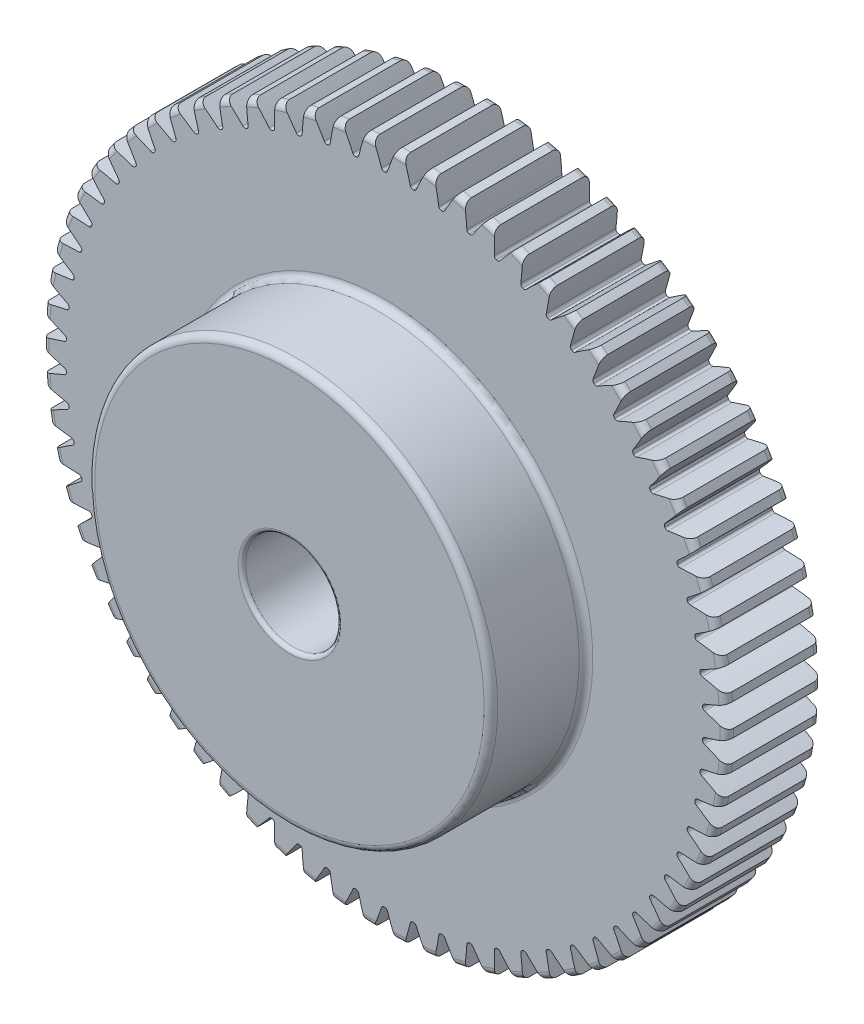
SolidWorks part; units mm, degrees
material "AISI 1020"
ref_plane "Front Plane" through (0, 0, 0) normal (0, 0, 1) x (1, 0, 0)
ref_plane "Top Plane" through (0, 0, 0) normal (0, 1, 0) x (1, 0, 0)
ref_plane "Right Plane" through (0, 0, 0) normal (1, 0, 0) x (0, 0, -1)
sketch "Sketch1" plane through (0, 0, 0) normal (0, 0, 1) x (1, 0, 0)
  line L0 (-889, 0) -> (889, 0) construction
  circle A0 centre (0, 0) radius 45.72 construction
  circle A1 centre (0, 0) radius 44.45 construction
  circle A2 centre (0, 0) radius 42.545 construction
  circle A3 centre (0, 0) radius 26.924 construction
  circle A4 centre (0, 0) radius 6.35 construction
  dimension "D2" = 1.27
  dimension "D3" = 3.175
  dimension "D1" = 3.175
sketch "Sketch2" plane through (0, 0, 0) normal (1, 0, 0) x (0, 0, -1)
  line L0 (0, 0) -> (-12.7, 0) construction
  line L1 (-12.7, 0) -> (-25.4, 0) construction
  dimension "Overall Width" = 25.4
  dimension "Face Width" = 12.7
sketch "Sketch4" plane through (0, 0, 0) normal (1, 0, 0) x (0, 0, -1)
  line L0 (-25.4, 6.35) -> (-25.4, 26.924)
  line L1 (-25.4, 26.924) -> (-12.7, 26.924)
  line L2 (-12.7, 26.924) -> (-12.7, 45.72)
  line L3 (-12.7, 45.72) -> (0, 45.72)
  line L4 (0, 45.72) -> (0, 6.35)
  line L5 (-12.7, 26.924) -> (-12.7, 0) construction
  line L6 (0, 45.72) -> (0, -45.72) construction
  line L7 (-12.7, 26.924) -> (0, 26.924) construction
  line L12 (-25.4, 6.35) -> (0, 6.35)
revolve "Revolve1" add sketch "Sketch4" angle 360 about L1
fillet "Fillet2" radius 0.9144 4 edges at (0, 26.924, 25.4) (0, 26.924, 12.7) (0, 45.72, 12.7) (0, 45.72, 0)
sketch "Sketch7" plane through (0, 0, 12.7) normal (0, 0, 1) x (1, 0, 0)
  line L0 (0, 0) -> (0, 45.72) construction
  line L1 (0.9974, 44.4388) -> (1.4871, 45.6958) construction
  line L3 (2.0512, 45.674) -> (1.9942, 44.4052) construction
  line L4 (1.9942, 44.4052) -> (1.9088, 42.5022) construction
  line L5 (0, 0) -> (1.9088, 42.5022) construction
  line L6 (0.9974, 44.4388) -> (0, 0) construction
  line L7 (0.9974, 44.4388) -> (1.0259, 45.7085) construction
  line L8 (0.9974, 44.4388) -> (0, 0) construction
  circle A0 centre (0, 0) radius 45.72 construction
  arc A1 (-0.0358, 42.545) -> (0.0358, 42.545) centre (0, 0) cw
  circle A2 centre (0, 0) radius 42.545 construction
  arc A3 (-0.9974, 44.4388) -> (0.9974, 44.4388) centre (0, 0) cw construction
  circle A4 centre (0, 0) radius 44.45 construction
  arc A5 (2.5931, 45.6464) -> (1.509, 45.6951) centre (0, 0) ccw construction
  arc A6 (0.9974, 44.4388) -> (2.9901, 44.3493) centre (0, 0) cw construction
  arc A7 (-1.509, 45.6951) -> (1.509, 45.6951) centre (0, 0) cw
  arc A8 (0.3963, 42.8017) -> (1.509, 45.6951) centre (42.4151, 28.3026) cw
  arc A9 (-0.3963, 42.8017) -> (-1.509, 45.6951) centre (-42.4151, 28.3026) ccw
  arc A10 (-0.0358, 42.545) -> (-0.3963, 42.8017) centre (-0.0361, 42.926) cw
  arc A11 (0.0358, 42.545) -> (0.3963, 42.8017) centre (0.0361, 42.926) ccw
  point P26 (-0.3082, 42.5439)
  point P29 (0.3082, 42.5439)
  dimension "D4" = 0.381
  dimension "D5" = 44.45
  dimension "D3" = 20
  dimension "D1" = 3.9898
  dimension "D2" = 1.9949
extrude "Cut-Extrude2" cut sketch "Sketch7" against normal through all
pattern_circular "CirPattern1" count 70 over 360 about axis through (0, 0, 25.4) along (0, 0, -1) of "Cut-Extrude2"
fillet "Fillet3" radius 0.508 2 edges at (0, 6.35, 0) (0, 6.35, 25.4)
sketch "Sketch8" plane through (0, 0, 0) normal (0, 0, -1) x (-1, 0, 0)
  line L1 (-1.651, 7.7826) -> (1.651, 7.7826)
  line L2 (-1.651, 7.7826) -> (-1.651, 4.4806)
  line L3 (-1.651, 4.4806) -> (1.651, 4.4806)
  line L4 (1.651, 7.7826) -> (1.651, 4.4806)
  circle A1 centre (0, 0) radius 6.35 construction
  point P4 (0, 4.4806)
  point P6 (0, 0)
  point P7 (-1.651, 6.1316)
  point P9 (0, 0)
  dimension "D1" = 3.302
  dimension "D2" = 3.302
extrude "Cut-Extrude3" cut sketch "Sketch8" against normal blind 12.7
equation "\"D1@Sketch1\"=2.5*(\"Pitch Dia.@Sketch1\"/\"Number of Teeth@Sketch1\")"
equation "\"D1@CirPattern1\"=\"Number of Teeth@Sketch1\""
equation "\"D1@Fillet2\"=\"OD@Sketch1\"*.01"
equation "\"D1@Sketch7\"=3.14159*(\"Pitch Dia.@Sketch1\"/\"Number of Teeth@Sketch1\")"
equation "\"D2@Sketch7\"=\"D1@Sketch7\"/2"
equation "\"D4@Sketch7\"=\"D1@Sketch7\"*.0955"
equation "\"D5@Sketch7\"=\"Pitch Dia.@Sketch1\"/2"
